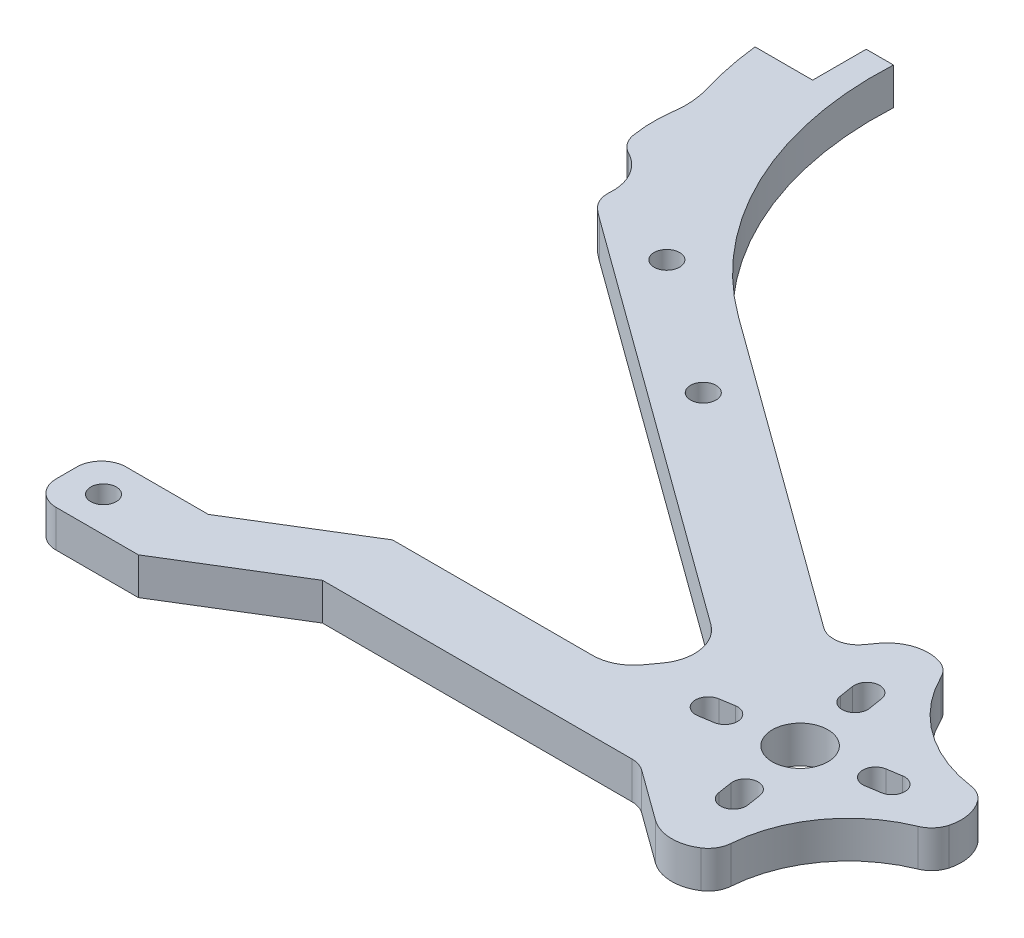
SolidWorks part; units mm, degrees
material "PPS"
ref_plane "前视基准面" through (0, 0, 0) normal (0, 0, 1) x (1, 0, 0)
ref_plane "上视基准面" through (0, 0, 0) normal (0, 1, 0) x (1, 0, 0)
ref_plane "右视基准面" through (0, 0, 0) normal (1, 0, 0) x (0, 0, -1)
sketch "草图3" plane through (0, 0, 0) normal (0, 1, 0) x (1, 0, 0)
  line L0 (0, 0) -> (35.4735, 0) construction
  line L1 (0, 0) -> (62.3757, -45.3186) construction
  line L2 (41.1319, -24.0128) -> (94.6944, -62.9282)
  line L3 (94.6944, -62.9282) -> (100.1314, -55.4448)
  line L4 (100.1314, -55.4448) -> (122.7839, -71.9028)
  line L5 (122.7839, -71.9028) -> (106.3259, -94.5552)
  line L6 (83.6734, -78.0972) -> (106.3259, -94.5552) construction
  line L9 (77.9994, -109.7251) -> (128.6275, -40.0415) construction
  line L11 (103.2286, -75) -> (90.242, -77.0569) construction
  line L13 (111.1302, -73.7485) -> (112.8586, -73.4748) construction
  line L14 (110.8877, -72.2176) -> (112.6161, -71.9438)
  line L15 (111.3726, -75.2794) -> (113.1011, -75.0057)
  line L16 (101.9772, -67.0985) -> (101.7034, -65.37) construction
  line L17 (103.5081, -66.856) -> (103.2343, -65.1276)
  line L18 (100.4463, -67.341) -> (100.1725, -65.6125)
  line L19 (95.3271, -76.2515) -> (93.5987, -76.5252) construction
  line L20 (95.5696, -77.7824) -> (93.8412, -78.0562)
  line L21 (95.0847, -74.7206) -> (93.3562, -74.9943)
  line L22 (104.4801, -82.9015) -> (104.7539, -84.63) construction
  line L23 (102.9492, -83.144) -> (103.223, -84.8724)
  line L24 (106.011, -82.659) -> (106.2848, -84.3875)
  line L36 (68.8077, -72) -> (90.242, -72) construction
  line L49 (89.1104, -70.6138) -> (83.6734, -78.0972)
  line L50 (35.5479, -31.6984) -> (89.1104, -70.6138)
  line L51 (83.6734, -78.0972) -> (30, -78.0972) construction
  line L52 (30, -78.0972) -> (30, -86.5972) construction
  line L53 (30, -86.5972) -> (95.3727, -86.5972) construction
  line L54 (95.3727, -86.5972) -> (106.3259, -94.5552)
  line L55 (83.6734, -78.0972) -> (56.8367, -78.0972)
  line L56 (95.3727, -86.5972) -> (56.8367, -86.5972)
  line L57 (56.8367, -78.0972) -> (42.9738, -86.5972)
  line L58 (42.9738, -86.5972) -> (30, -86.5972)
  line L59 (56.8367, -86.5972) -> (42.9738, -95.0972)
  line L60 (30, -86.5972) -> (30, -95.0972)
  line L61 (30, -95.0972) -> (42.9738, -95.0972)
  circle A5 centre (103.2286, -75) radius 3.375
  arc A6 (110.8877, -72.2176) -> (111.3726, -75.2794) centre (111.1302, -73.7485) ccw
  arc A7 (113.1011, -75.0057) -> (112.6161, -71.9438) centre (112.8586, -73.4748) ccw
  arc A8 (103.5081, -66.856) -> (100.4463, -67.341) centre (101.9772, -67.0985) cw
  arc A9 (100.1725, -65.6125) -> (103.2343, -65.1276) centre (101.7034, -65.37) cw
  arc A10 (95.5696, -77.7824) -> (95.0847, -74.7206) centre (95.3271, -76.2515) ccw
  arc A11 (93.3562, -74.9943) -> (93.8412, -78.0562) centre (93.5987, -76.5252) ccw
  arc A12 (102.9492, -83.144) -> (106.011, -82.659) centre (104.4801, -82.9015) cw
  arc A13 (106.2848, -84.3875) -> (103.223, -84.8724) centre (104.7539, -84.63) cw
  arc A16 (41.1319, -24.0128) -> (35.5479, -31.6984) centre (38.3399, -27.8556) ccw
  circle A17 centre (103.2286, -75) radius 66.25 construction
  circle A18 centre (44.0442, -32) radius 1.55
  circle A19 centre (60.2246, -43.7557) radius 1.55
  circle A20 centre (34.5, -90.8472) radius 1.55
  point P11 (114.5549, -83.229)
  point P20 (111.9944, -73.6116)
  point P27 (101.8403, -66.2343)
  point P35 (94.4629, -76.3884)
  point P42 (104.617, -83.7657)
  point P54 (94.9997, -86.3262)
  point P69 (30, -90.8472)
  dimension "D2" = 45
  dimension "D3" = 6.75
  dimension "D4" = 1.55
  dimension "D7" = 14
  dimension "D11" = 132.5
  dimension "D12" = 3.1
  dimension "D16" = 3.1
  dimension "D1" = 36
  dimension "D5" = 1.75
  dimension "D6" = 8
  dimension "D8" = 14
  dimension "D9" = 4.75
  dimension "D10" = 75
  dimension "D13" = 32
  dimension "D14" = 20
  dimension "D15" = 8.5
  dimension "D17" = 34.5
  dimension "D18" = 4.5
  dimension "D19" = 90.8472
  dimension "D22" = 72
extrude "凸台-拉伸1" add sketch "草图3" along normal blind 4.5
fillet "圆角-美观1" radius 5 5 edges at (100.1314, 2.25, 55.4448) (122.7839, 2.25, 71.9028) (89.1104, 2.25, 70.6138) (106.3259, 2.25, 94.5552) (83.6734, 2.25, 78.0972)
sketch "草图4" plane through (0, 4.5, 0) normal (0, 1, 0) x (1, 0, 0)
  line L0 (104.1765, -58.3837) -> (118.7388, -68.9638)
  line L1 (119.8449, -75.9478) -> (109.2648, -90.5101)
  line L3 (103.2286, -75) -> (124.6569, -90.5685) construction
  line L4 (103.2286, -75) -> (89.033, -94.5387) construction
  line L5 (87.7185, -81.0362) -> (102.2808, -91.6163)
  arc A2 (102.2808, -91.6163) -> (87.7185, -81.0362) centre (86.1651, -98.4859) ccw
  arc A8 (118.7388, -68.9638) -> (104.1765, -58.3837) centre (120.2922, -51.5141) cw
  arc A9 (119.8449, -75.9478) -> (109.2648, -90.5101) centre (124.6569, -90.5685) ccw
  line M2 (118.7388, -68.9638) -> (104.1765, -58.3837)
  line M12 (109.2648, -90.5101) -> (119.8449, -75.9478)
extrude "圆弧-美观2" cut sketch "草图4" against normal up to next contours A8 M2 | A9 M12 region at (110.8688, 4.5, 64.4842) region at (113.6066, 4.5, 82.54)
fillet "圆角-美观3" radius 3 8 edges at (104.1765, 2.25, 58.3837) (118.7388, 2.25, 68.9638) (119.8449, 2.25, 75.9478) (94.6944, 2.25, 62.9282) (109.2648, 2.25, 90.5101) (30, 2.25, 95.0972) (95.3727, 2.25, 86.5972) (30, 2.25, 86.5972)
sketch "草图5" plane through (0, 0, 0) normal (0, 1, 0) x (1, 0, 0)
  line L0 (0, 0) -> (158.8801, 0) construction
  line L1 (0, 0) -> (0, -78.2587) construction
  line L2 (29.255, -13.8932) -> (40.1931, -23.471) construction
  line L3 (27.0025, -4.25) -> (34, -4.25)
  line L4 (34, -4.25) -> (34, 2.25)
  line L5 (34, -3.25) -> (26.9026, -3.25) construction
  line L6 (34, 3.25) -> (34, -3.25) construction
  line L7 (37.3772, 3.25) -> (34, 3.25) construction
  line L8 (41.1319, -24.0128) -> (54.395, -33.649)
  line L9 (34, 2.25) -> (37.3109, 2.25)
  line L10 (35.5479, -31.6984) -> (85.0653, -67.6749) construction
  line L11 (41.1319, -24.0128) -> (35.5479, -31.6984)
  arc A0 (26.9026, -3.25) -> (28.5167, -11.6611) centre (68.8233, 0.4342) ccw construction
  arc A5 (41.1319, -24.0128) -> (40.1931, -23.471) centre (38.2952, -27.8445) ccw
  arc A7 (40.1931, -23.471) -> (35.5479, -31.6984) centre (38.3022, -27.8285) ccw construction
  arc A8 (35.5479, -31.6984) -> (28.8424, -15.919) centre (45.3379, -18.2237) cw
  arc A9 (28.8424, -15.919) -> (28.5167, -11.6611) centre (18.9386, -14.5353) ccw
  arc A11 (37.3772, 3.25) -> (54.395, -33.649) centre (78.8424, 0) ccw
  arc A12 (27.0025, -4.25) -> (28.5167, -11.6611) centre (68.8233, 0.4342) ccw
  arc A13 (29.8202, 19.4008) -> (29.8202, -19.4008) centre (91.9966, 0) ccw construction
  arc A14 (54.395, 33.649) -> (54.395, -33.649) centre (78.8424, 0) ccw construction
  arc A15 (29.9602, 19.3706) -> (29.9602, -19.3706) centre (67.3193, 0) ccw construction
  dimension "D1" = 3.25
  dimension "D2" = 3.25
  dimension "D3" = 34
  dimension "D4" = 1
  dimension "D5" = 1
extrude "机臂配合防旋转" add sketch "草图5" along normal up to surface (4.5 mm away) contours L7 A0 A9 A8 A7 A5 L8 region at (35.1434, 0, 16.2105) up to face at (60.2246, 4.5, 45.3057)
sketch "草图7" plane through (0, 0, 0) normal (0, 1, 0) x (1, 0, 0)
  circle A6 centre (28, -28) radius 3.15 construction
  circle A7 centre (28, -28) radius 5.5
  circle A8 centre (44.0442, -32) radius 1.55 construction
  point P5 (0, 0)
  point P7 (44.0201, -30.4502)
  dimension "D1" = 11
  dimension "D2" = 16.0442
  dimension "D3" = 4
extrude "减震球让位" cut sketch "草图7" along normal through all
fillet "圆角1" radius 3 2 edges at (33.2399, 2.25, 29.6714) (29.2815, 2.25, 22.6514)
